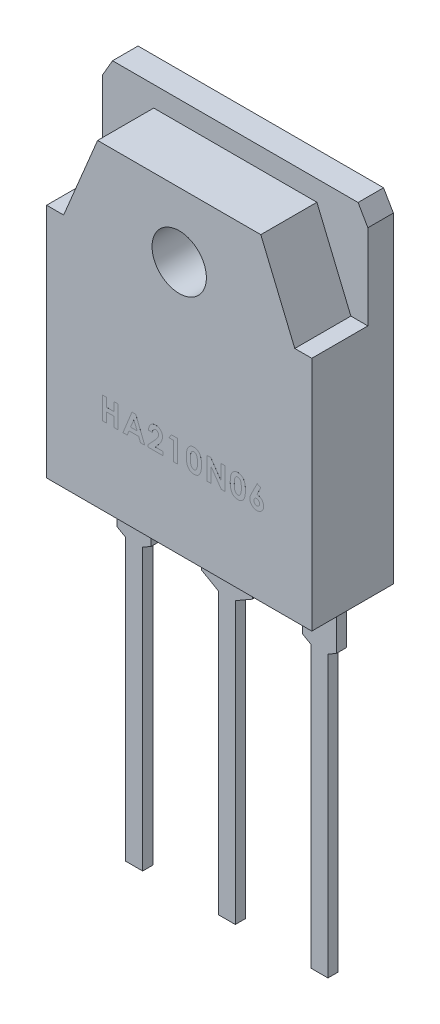
SolidWorks part; units mm, degrees
ref_plane "Front Plane" through (0, 0, 0) normal (0, 0, 1) x (1, 0, 0)
ref_plane "Top Plane" through (0, 0, 0) normal (0, 1, 0) x (1, 0, 0)
ref_plane "Right Plane" through (0, 0, 0) normal (1, 0, 0) x (0, 0, -1)
sketch "Sketch1" plane through (0, 0, 0) normal (0, 0, 1) x (1, 0, 0)
  line L1 (0, 0) -> (15.6, 0)
  line L2 (0, 0) -> (0, 19.9)
  line L3 (0, 19.9) -> (15.6, 19.9)
  line L4 (15.6, 0) -> (15.6, 19.9)
  dimension "D1" = 15.6
  dimension "D2" = 19.9
extrude "MAIN BODY" add sketch "Sketch1" along normal blind 1.5
sketch "Sketch3" plane through (0, 0, 1.5) normal (0, 0, 1) x (1, 0, 0)
  line L0 (15.6, 0) -> (15.6, 19.9) construction
  line L1 (0, 0) -> (15.6, 0)
  line L2 (0, 0) -> (0, 13.9)
  line L3 (0, 13.9) -> (15.6, 13.9)
  line L4 (15.6, 0) -> (15.6, 13.9)
  line L5 (15.6, 19.9) -> (0, 19.9) construction
  dimension "D1" = 6
extrude "FRONT BODY" add sketch "Sketch3" along normal blind 3.3 and the other way up to next (1.5 mm away)
sketch "Sketch5" plane through (0, 0, 0) normal (0, -1, 0) x (1, 0, 0)
  line L0 (7.8, 0) -> (7.8, 1.4) construction
  line L1 (6.8, 2) -> (8.8, 2)
  line L2 (6.8, 2) -> (6.8, 1.4)
  line L3 (6.8, 1.4) -> (8.8, 1.4)
  line L4 (8.8, 2) -> (8.8, 1.4)
  line L5 (0, 0) -> (15.6, 0) construction
  line L11 (6.8, 2) -> (8.8, 2)
  line L12 (6.8, 2) -> (6.8, 1.4)
  line L13 (6.8, 1.4) -> (8.8, 1.4)
  line L14 (8.8, 2) -> (8.8, 1.4)
  line L19 (4.26, 2) -> (6.26, 2) [skipped]
  line L20 (4.26, 2) -> (4.26, 1.4) [skipped]
  line L21 (4.26, 1.4) -> (6.26, 1.4) [skipped]
  line L22 (6.26, 2) -> (6.26, 1.4) [skipped]
  line L23 (9.34, 2) -> (11.34, 2) [skipped]
  line L24 (9.34, 2) -> (9.34, 1.4) [skipped]
  line L25 (9.34, 1.4) -> (11.34, 1.4) [skipped]
  line L26 (11.34, 2) -> (11.34, 1.4) [skipped]
  dimension "D1" = 2
  dimension "D2" = 0.6
  dimension "D4" = 1.4
  dimension "D5" = 2
  dimension "D6" = 2
extrude "LEG BASE" add sketch "Sketch5" along normal blind 3.5
sketch "Sketch6" plane through (0, -3.5, 0) normal (0, -1, 0) x (1, 0, 0)
  line L0 (6.8, 1.4) -> (8.8, 1.4) construction
  line L1 (6.8, 2) -> (8.8, 2) construction
  line L5 (7.3, 2) -> (8.3, 2)
  line L6 (7.3, 2) -> (7.3, 1.4)
  line L7 (7.3, 1.4) -> (8.3, 1.4)
  line L8 (8.3, 2) -> (8.3, 1.4)
  line L9 (6.8, 1.4) -> (8.8, 1.4) construction
  point P0 (7.8, 2)
  dimension "D1" = 1
extrude "BASE" add sketch "Sketch6" along normal blind 16.5
sketch "Sketch11" plane through (0, 0, 1.5) normal (0, 0, 1) x (1, 0, 0)
  line L0 (1, 13.9) -> (3, 18.7)
  line L1 (15.6, 13.9) -> (0, 13.9) construction
  line L2 (3, 18.7) -> (12.6, 18.7)
  line L3 (12.6, 18.7) -> (14.6, 13.9)
  line L4 (14.6, 13.9) -> (1, 13.9)
  line L5 (7.8, 13.9) -> (7.8, 18.7) construction
  line L6 (0, 0) -> (15.6, 0) construction
  dimension "D1" = 9.6
  dimension "D2" = 18.7
  dimension "D3" = 13.6
extrude "TOP BODY" add sketch "Sketch11" along normal up to surface (3.3 mm away) up to face at (7.8, 6.95, 4.8)
hole_wizard "Ø3.2 (3.2) Diameter Hole1" positions "Sketch12" profile "Sketch13" hole size "Ø3.2" standard "ANSI Metric" end condition through all
sketch "Sketch12" plane through (0, 0, 4.8) normal (0, 0, 1) x (1, 0, 0)
  line L0 (7.8, 0) -> (7.8, 14.9) construction
  line L1 (0, 0) -> (15.6, 0) construction
  point P0 (7.8, 14.9)
  dimension "D1" = 14.9
sketch "Sketch13" plane through (7.8, 14.9, 4.8) normal (1, 0, 0) x (0, -1, 0)
  line L0 (0, 0) -> (0, 4.8)
  line L1 (0, 4.8) -> (1.6, 4.8)
  line L2 (1.6, 4.8) -> (1.6, 0)
  line L5 (1.6, 0) -> (0, 0)
  line L11 (0, -6.35) -> (0, 107.95) construction
  dimension "Thru Hole Dia." = 3.2
  dimension "Thru Hole Depth" = 4.8
sketch "Sketch10" plane through (0, 0, 4.8) normal (0, 0, 1) x (1, 0, 0)
  text T0 "<b>HA210N06</b>\r\n" font "Century Gothic" height in points 5
extrude "PN" add sketch "Sketch10" along normal blind 0.001
pattern_linear "LPattern1" count 2 spacing 5.45 along (1, 0, 0) count 2 spacing 5.45 along (-1, 0, 0) of "LEG BASE", "BASE"
sketch "Sketch14" plane through (0, 0, 2) normal (0, 0, 1) x (1, 0, 0)
  line L0 (6.8, 0) -> (8.8, 0) construction
  line L1 (6.3, 0) -> (9.3, 0)
  line L2 (6.3, 0) -> (6.3, -3.5)
  line L3 (6.3, -3.5) -> (9.3, -3.5)
  line L4 (9.3, 0) -> (9.3, -3.5)
  line L5 (6.8, -3.5) -> (7.3, -3.5) construction
  point P4 (7.8, 0)
  dimension "D1" = 3
extrude "Boss-Extrude10" add sketch "Sketch14" against normal up to surface (0.6 mm away) up to face at (7.7375, -8.8125, 1.4)
chamfer "Chamfer1" distance 0.5 angle 30 12 edges at (14.25, -3.5, 1.7) (12.25, -3.5, 1.7) (3.35, -3.5, 1.7) (1.35, -3.5, 1.7)
chamfer "Chamfer2" distance 1 angle 30 2 edges at (9.3, -3.5, 1.7) (6.3, -3.5, 1.7)
chamfer "Chamfer3" distance 1 angle 30 2 edges at (15.6, 19.9, 0.75) (0, 19.9, 0.75)
